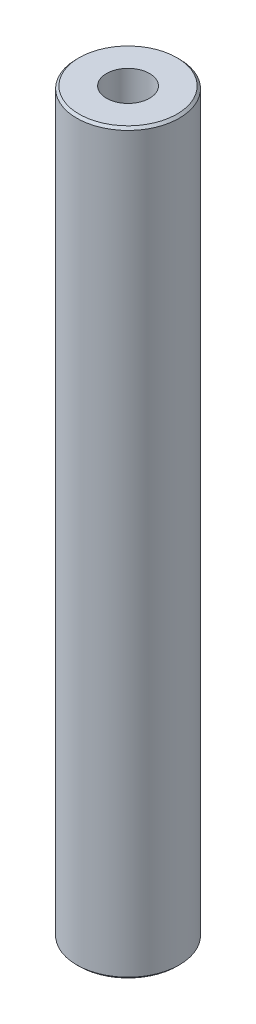
SolidWorks part; units mm, degrees
ref_plane "Front Plane" through (0, 0, 0) normal (0, 0, 1) x (1, 0, 0)
ref_plane "Top Plane" through (0, 0, 0) normal (0, 1, 0) x (1, 0, 0)
ref_plane "Right Plane" through (0, 0, 0) normal (1, 0, 0) x (0, 0, -1)
sketch "Sketch1" plane through (0, 0, 0) normal (0, 1, 0) x (1, 0, 0)
  circle A0 centre (0, 0) radius 25
  dimension "SHAFT_OD" = 50
extrude "Boss-Extrude1" add sketch "Sketch1" along normal blind 359.9076
sketch "Sketch2" plane through (0, 0, 0) normal (0, 1, 0) x (1, 0, 0)
  circle A0 centre (0, 0) radius 10.4973
  dimension "BORE_D" = 20.9946
extrude "Cut-Extrude1" cut sketch "Sketch2" along normal through all
chamfer "Chamfer1" distance 1.1473 angle 45 2 edges at (0, 359.9076, 25) (0, 0, 25)
